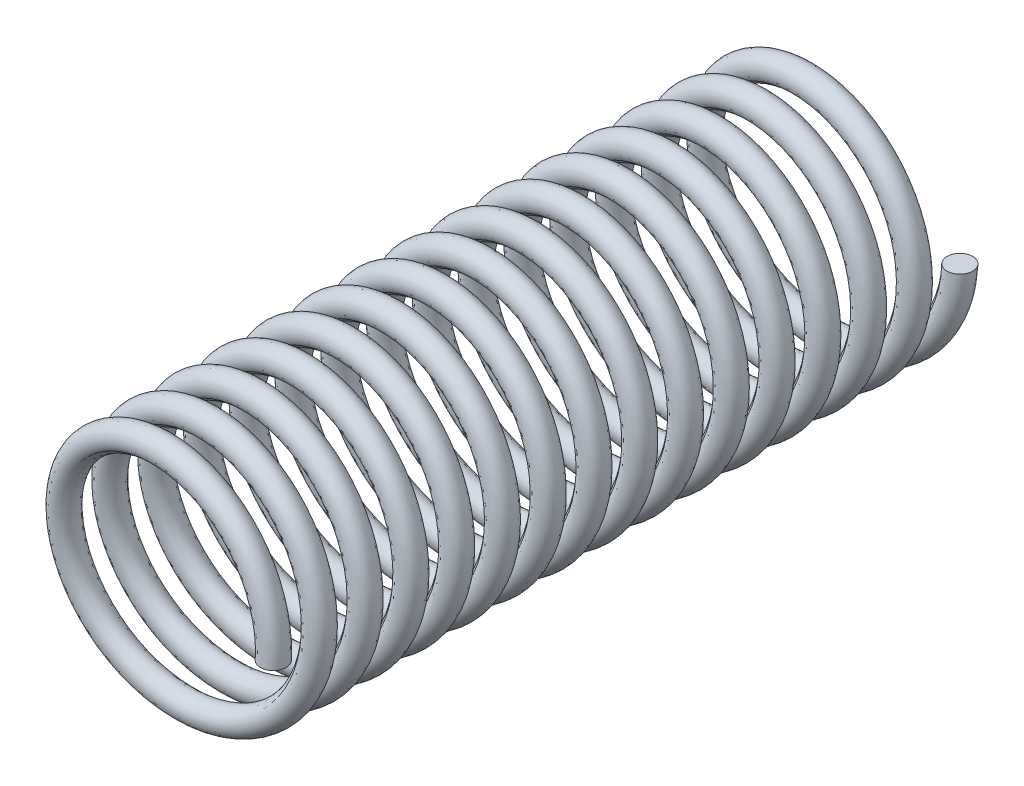
SolidWorks part; units mm, degrees
note: '?' marks a value the reader was unsure of.
ref_plane "Front Plane" through (0, 0, 0) normal (0, 0, 1) x (1, 0, 0)
ref_plane "Top Plane" through (0, 0, 0) normal (0, 1, 0) x (1, 0, 0)
ref_plane "Right Plane" through (0, 0, 0) normal (1, 0, 0) x (0, 0, -1)
sketch "Sketch1" plane through (0, 0, 0) normal (0, 0, 1) x (1, 0, 0)
  circle A0 centre (0, 0) radius 3.2163
  dimension "D1" = 6.4325
curve "Helix/Spiral1" pitch 1.27 height 19.05 turns 15
sketch "Sketch2" plane through (0, 0, 0) normal (0, 1, 0) x (1, 0, 0)
  circle A0 centre (3.2163, 0) radius 0.3556
  spline S0 degree 3 poles (3.2163, 0) (3.2163, -0.0263) (3.0488, -0.0795) (2.3335, -0.1587) (1.2629, -0.2381) (0, -0.3175) (-1.2629, -0.3969) (-2.3335, -0.4762) (-3.0488, -0.5556) (-3.3, -0.635) (-3.0488, -0.7144) (-2.3335, -0.7937) (-1.2629, -0.8731) (0, -0.9525) (1.2629, -1.0319) (2.3335, -1.1112) (3.0488, -1.1906) (3.3, -1.27) (3.0488, -1.3494) (2.3335, -1.4287) (1.2629, -1.5081) (0, -1.5875) (-1.2629, -1.6669) (-2.3335, -1.7463) (-3.0488, -1.8256) (-3.3, -1.905) (-3.0488, -1.9844) (-2.3335, -2.0637) (-1.2629, -2.1431) (0, -2.2225) (1.2629, -2.3019) (2.3335, -2.3813) (3.0488, -2.4606) (3.3, -2.54) (3.0488, -2.6194) (2.3335, -2.6988) (1.2629, -2.7781) (0, -2.8575) (-1.2629, -2.9369) (-2.3335, -3.0162) (-3.0488, -3.0956) (-3.3, -3.175) (-3.0488, -3.2544) (-2.3335, -3.3338) (-1.2629, -3.4131) (0, -3.4925) (1.2629, -3.5719) (2.3335, -3.6512) (3.0488, -3.7306) (3.3, -3.81) (3.0488, -3.8894) (2.3335, -3.9687) (1.2629, -4.0481) (0, -4.1275) (-1.2629, -4.2069) (-2.3335, -4.2862) (-3.0488, -4.3656) (-3.3, -4.445) (-3.0488, -4.5244) (-2.3335, -4.6037) (-1.2629, -4.6831) (0, -4.7625) (1.2629, -4.8419) (2.3335, -4.9212) (3.0488, -5.0006) (3.3, -5.08) (3.0488, -5.1594) (2.3335, -5.2387) (1.2629, -5.3181) (0, -5.3975) (-1.2629, -5.4769) (-2.3335, -5.5562) (-3.0488, -5.6356) (-3.3, -5.715) (-3.0488, -5.7944) (-2.3335, -5.8737) (-1.2629, -5.9531) (0, -6.0325) (1.2629, -6.1119) (2.3335, -6.1912) (3.0488, -6.2706) (3.3, -6.35) (3.0488, -6.4294) (2.3335, -6.5087) (1.2629, -6.5881) (0, -6.6675) (-1.2629, -6.7469) (-2.3335, -6.8262) (-3.0488, -6.9056) (-3.3, -6.985) (-3.0488, -7.0644) (-2.3335, -7.1437) (-1.2629, -7.2231) (0, -7.3025) (1.2629, -7.3819) (2.3335, -7.4612) (3.0488, -7.5406) (3.3, -7.62) (3.0488, -7.6994) (2.3335, -7.7787) (1.2629, -7.8581) (0, -7.9375) (-1.2629, -8.0169) (-2.3335, -8.0962) (-3.0488, -8.1756) (-3.3, -8.255) (-3.0488, -8.3344) (-2.3335, -8.4137) (-1.2629, -8.4931) (0, -8.5725) (1.2629, -8.6519) (2.3335, -8.7312) (3.0488, -8.8106) (3.3, -8.89) (3.0488, -8.9694) (2.3335, -9.0487) (1.2629, -9.1281) (0, -9.2075) (-1.2629, -9.2869) (-2.3335, -9.3662) (-3.0488, -9.4456) (-3.3, -9.525) (-3.0488, -9.6044) (-2.3335, -9.6837) (-1.2629, -9.7631) (0, -9.8425) (1.2629, -9.9219) (2.3335, -10.0012) (3.0488, -10.0806) (3.3, -10.16) (3.0488, -10.2394) (2.3335, -10.3187) (1.2629, -10.3981) (0, -10.4775) (-1.2629, -10.5569) (-2.3335, -10.6362) (-3.0488, -10.7156) (-3.3, -10.795) (-3.0488, -10.8744) (-2.3335, -10.9537) (-1.2629, -11.0331) (0, -11.1125) (1.2629, -11.1919) (2.3335, -11.2712) (3.0488, -11.3506) (3.3, -11.43) (3.0488, -11.5094) (2.3335, -11.5887) (1.2629, -11.6681) (0, -11.7475) (-1.2629, -11.8269) (-2.3335, -11.9062) (-3.0488, -11.9856) (-3.3, -12.065) (-3.0488, -12.1444) (-2.3335, -12.2237) (-1.2629, -12.3031) (0, -12.3825) (1.2629, -12.4619) (2.3335, -12.5412) (3.0488, -12.6206) (3.3, -12.7) (3.0488, -12.7794) (2.3335, -12.8587) (1.2629, -12.9381) (0, -13.0175) (-1.2629, -13.0969) (-2.3335, -13.1762) (-3.0488, -13.2556) (-3.3, -13.335) (-3.0488, -13.4144) (-2.3335, -13.4937) (-1.2629, -13.5731) (0, -13.6525) (1.2629, -13.7319) (2.3335, -13.8112) (3.0488, -13.8906) (3.3, -13.97) (3.0488, -14.0494) (2.3335, -14.1287) (1.2629, -14.2081) (0, -14.2875) (-1.2629, -14.3669) (-2.3335, -14.4462) (-3.0488, -14.5256) (-3.3, -14.605) (-3.0488, -14.6844) (-2.3335, -14.7637) (-1.2629, -14.8431) (0, -14.9225) (1.2629, -15.0019) (2.3335, -15.0812) (3.0488, -15.1606) (3.3, -15.24) (3.0488, -15.3194) (2.3335, -15.3987) (1.2629, -15.4781) (0, -15.5575) (-1.2629, -15.6369) (-2.3335, -15.7162) (-3.0488, -15.7956) (-3.3, -15.875) (-3.0488, -15.9544) (-2.3335, -16.0337) (-1.2629, -16.1131) (0, -16.1925) (1.2629, -16.2719) (2.3335, -16.3512) (3.0488, -16.4306) (3.3, -16.51) (3.0488, -16.5894) (2.3335, -16.6687) (1.2629, -16.7481) (0, -16.8275) (-1.2629, -16.9069) (-2.3335, -16.9862) (-3.0488, -17.0656) (-3.3, -17.145) (-3.0488, -17.2244) (-2.3335, -17.3037) (-1.2629, -17.3831) (0, -17.4625) (1.2629, -17.5419) (2.3335, -17.6212) (3.0488, -17.7006) (3.3, -17.78) (3.0488, -17.8594) (2.3335, -17.9388) (1.2629, -18.0181) (0, -18.0975) (-1.2629, -18.1769) (-2.3335, -18.2563) (-3.0488, -18.3356) (-3.3, -18.415) (-3.0488, -18.4944) (-2.3335, -18.5738) (-1.2629, -18.6531) (0, -18.7325) (1.2629, -18.8119) (2.3335, -18.8913) (3.0488, -18.9705) (3.2163, -19.0237) (3.2163, -19.05) knots 0 0 0 0 0.004167 0.008333 0.0125 0.016667 0.020833 0.025 0.029167 0.033333 0.0375 0.041667 0.045833 0.05 0.054167 0.058333 0.0625 0.066667 0.070833 0.075 0.079167 0.083333 0.0875 0.091667 0.095833 0.1 0.104167 0.108333 0.1125 0.116667 0.120833 0.125 0.129167 0.133333 0.1375 0.141667 0.145833 0.15 0.154167 0.158333 0.1625 0.166667 0.170833 0.175 0.179167 0.183333 0.1875 0.191667 0.195833 0.2 0.204167 0.208333 0.2125 0.216667 0.220833 0.225 0.229167 0.233333 0.2375 0.241667 0.245833 0.25 0.254167 0.258333 0.2625 0.266667 0.270833 0.275 0.279167 0.283333 0.2875 0.291667 0.295833 0.3 0.304167 0.308333 0.3125 0.316667 0.320833 0.325 0.329167 0.333333 0.3375 0.341667 0.345833 0.35 0.354167 0.358333 0.3625 0.366667 0.370833 0.375 0.379167 0.383333 0.3875 0.391667 0.395833 0.4 0.404167 0.408333 0.4125 0.416667 0.420833 0.425 0.429167 0.433333 0.4375 0.441667 0.445833 0.45 0.454167 0.458333 0.4625 0.466667 0.470833 0.475 0.479167 0.483333 0.4875 0.491667 0.495833 0.5 0.504167 0.508333 0.5125 0.516667 0.520833 0.525 0.529167 0.533333 0.5375 0.541667 0.545833 0.55 0.554167 0.558333 0.5625 0.566667 0.570833 0.575 0.579167 0.583333 0.5875 0.591667 0.595833 0.6 0.604167 0.608333 0.6125 0.616667 0.620833 0.625 0.629167 0.633333 0.6375 0.641667 0.645833 0.65 0.654167 0.658333 0.6625 0.666667 0.670833 0.675 0.679167 0.683333 0.6875 0.691667 0.695833 0.7 0.704167 0.708333 0.7125 0.716667 0.720833 0.725 0.729167 0.733333 0.7375 0.741667 0.745833 0.75 0.754167 0.758333 0.7625 0.766667 0.770833 0.775 0.779167 0.783333 0.7875 0.791667 0.795833 0.8 0.804167 0.808333 0.8125 0.816667 0.820833 0.825 0.829167 0.833333 0.8375 0.841667 0.845833 0.85 0.854167 0.858333 0.8625 0.866667 0.870833 0.875 0.879167 0.883333 0.8875 0.891667 0.895833 0.9 0.904167 0.908333 0.9125 0.916667 0.920833 0.925 0.929167 0.933333 0.9375 0.941667 0.945833 0.95 0.954167 0.958333 0.9625 0.966667 0.970833 0.975 0.979167 0.983333 0.9875 0.991667 0.995833 1 1 1 1 construction
  dimension "D1" = 0.7112
sweep "Sweep1" add profiles "Sketch2" path "Helix/Spiral1"
ref_axis "Axis1" through (0, 0, -1.3437) along (0, 0, 1)?
sketch "Sketch3" plane through (0, 0, 0) normal (0, 1, 0) x (1, 0, 0)
  circle A0 centre (3.2163, 0) radius 0.3556 construction
  point P0 (3.2163, 0.3556)
sketch "Sketch4" plane through (0, 0, 0) normal (0, -1, 0) x (1, 0, 0)
  circle A0 centre (3.2163, 19.05) radius 0.3556 construction
  point P0 (3.2163, 19.4056)
